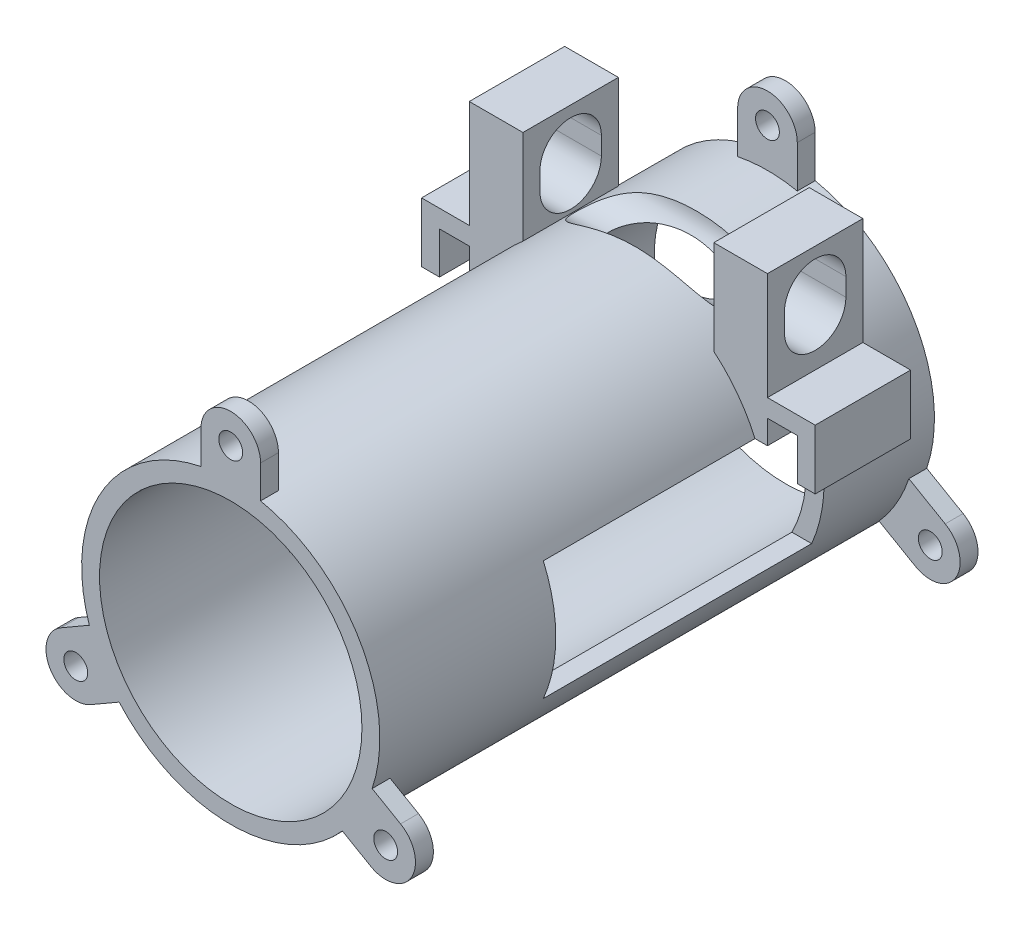
SolidWorks part; units mm, degrees
ref_plane "Front Plane" through (0, 0, 0) normal (0, 0, 1) x (1, 0, 0)
ref_plane "Top Plane" through (0, 0, 0) normal (0, 1, 0) x (1, 0, 0)
ref_plane "Right Plane" through (0, 0, 0) normal (1, 0, 0) x (0, 0, -1)
sketch "Sketch1" plane through (0, 0, 0) normal (0, 0, 1) x (1, 0, 0)
  circle A0 centre (0, 0) radius 22
  circle A1 centre (0, 0) radius 25
  dimension "D1" = 44
  dimension "D2" = 3
extrude "Boss-Extrude1" add sketch "Sketch1" along normal blind 40
ref_plane "Plane1" through (0, 0, 20) normal (0, 0, 1) x (1, 0, 0)
sketch "Sketch3" plane through (0, 0, 0) normal (1, 0, 0) x (0, 0, -1)
  line L0 (0, 25) -> (-40, 25) construction
  circle A0 centre (-20, 25) radius 5.15
  dimension "D1" = 10.3
extrude "Cut-Extrude1" cut sketch "Sketch3" against normal mid plane 50
sketch "Sketch4" plane through (0, 0, 20) normal (0, 0, 1) x (1, 0, 0)
  line L3 (0, 0) -> (50000, 0) construction
  line L4 (-19.776, 25) -> (49980.224, 25) construction
  line L5 (-16, 19.2094) -> (-16, 35)
  line L6 (-25, 0) -> (-25, 35)
  line L7 (-25, 35) -> (-16, 35)
  line L8 (0, 0) -> (0, 11.0861) construction
  arc A1 (-25, 0) -> (-16, 19.2094) centre (0, 0) cw
  circle A3 centre (0, 0) radius 25 construction
  point P14 (0, 0)
  point P15 (-25, -10.393)
  point P16 (0, 0)
  dimension "D1" = 9
  dimension "D2" = 35
extrude "Boss-Extrude2" add sketch "Sketch4" along normal mid plane 16
sketch "Sketch6" plane through (0, 0, 20) normal (0, 0, 1) x (1, 0, 0)
  line L0 (-25, 35) -> (-25, 0) construction
  line L1 (-25, 14) -> (-33, 14)
  line L2 (-25, 14) -> (-25, 17)
  line L3 (-25, 17) -> (-33, 17)
  line L4 (-33, 14) -> (-33, 17)
  line L5 (-25, 14) -> (-33, 17) construction
  line L6 (-25, 17) -> (-33, 14) construction
  line L7 (-33, 14) -> (-30, 14)
  line L8 (-33, 14) -> (-33, 7)
  line L9 (-33, 7) -> (-30, 7)
  line L10 (-30, 14) -> (-30, 7)
  line L11 (-33, 14) -> (-30, 7) construction
  line L12 (-33, 7) -> (-30, 14) construction
  point P4 (-29, 15.5)
  point P5 (-29, 10.725)
  point P6 (0, 0)
  point P13 (-31.5, 10.5)
  dimension "D1" = 8
  dimension "D2" = 3
  dimension "D3" = 7
  dimension "D4" = 3
  dimension "D5" = 7
sketch "Sketch5" plane through (-25, 0, 0) normal (-1, 0, 0) x (0, 0, 1)
  line L0 (20, -27.5) -> (20, 27.5) construction
  line L1 (20, 25) -> (20, 28) construction
  line L6 (14.85, 25) -> (14.85, 28)
  line L7 (25.15, 25) -> (25.15, 28)
  circle A0 centre (20, 25) radius 5.15 construction
  arc A1 (25.15, 25) -> (14.85, 25) centre (20, 25) ccw construction
  arc A2 (14.85, 25) -> (25.15, 25) centre (20, 25) ccw
  arc A3 (25.15, 28) -> (14.85, 28) centre (20, 28) ccw
  point P7 (20, 26.5)
  dimension "D1" = 3
extrude "Cut-Extrude3" cut sketch "Sketch5" against normal through all
extrude "Boss-Extrude3" add sketch "Sketch6" along normal mid plane 16 contours L10 L1 L8 L9 | L2 L1 L4 L3 region at (-31.5, 10.5, 20)
mirror "Mirror1" about plane through (0, 0, 0) normal (1, 0, 0) of "Cut-Extrude3", "Boss-Extrude3", "Boss-Extrude2"
sketch "Sketch7" plane through (0, 0, 40) normal (0, 0, 1) x (1, 0, 0)
  circle A0 centre (0, 0) radius 22
  circle A1 centre (0, 0) radius 25
extrude "Boss-Extrude4" add sketch "Sketch7" along normal blind 53
ref_plane "Plane2" through (-25, 0, 0) normal (-1, 0, 0) x (0, 0, 1)
sketch "Sketch8" plane through (-25, 0, 0) normal (-1, 0, 0) x (0, 0, 1)
  line L0 (20, -27.5) -> (20, 27.5) construction
  line L1 (18.5, 10) -> (63.5, 10)
  line L2 (18.5, 10) -> (18.5, -10)
  line L3 (18.5, -10) -> (63.5, -10)
  line L4 (63.5, 10) -> (63.5, -10)
  line L5 (18.5, 10) -> (63.5, -10) construction
  line L6 (18.5, -10) -> (63.5, 10) construction
  point P4 (41, 0)
  point P7 (0, 0)
  dimension "D1" = 21
  dimension "D2" = 45
  dimension "D3" = 20
extrude "Cut-Extrude4" cut sketch "Sketch8" against normal blind 50
sketch "Sketch9" plane through (0, 0, 0) normal (0, 0, -1) x (-1, 0, 0)
  line L0 (0, 0) -> (0, 31.533) construction
  line L1 (-5, 31.533) -> (-5, 24.4949)
  line L2 (5, 31.533) -> (5, 24.4949)
  circle A0 centre (0, 31.533) radius 2
  circle A1 centre (0, 31.533) radius 5
  circle A2 centre (0, 0) radius 25 construction
  arc A3 (-5, 24.4949) -> (5, 24.4949) centre (0, 0) cw
  circle A6 centre (0, 31.533) radius 2 construction
  point P13 (5, 24.4949)
  circle M3 centre (0, 0) radius 25
  dimension "D1" = 4
  dimension "D2" = 3
extrude "Boss-Extrude5" add sketch "Sketch9" against normal blind 3 contours A1 L1 M3 | A1 A3 A0 M3 | A1 L2 M3 region at (0, 26.4396, 0) region at (0, 36.3916, 0)
pattern_circular "CirPattern1" count 3 every 120 about axis through (0, 0, 0) along (0, 0, 1) of "Boss-Extrude5"
sketch "Sketch10" plane through (0, 0, 93) normal (0, 0, 1) x (1, 0, 0)
  line L0 (-5, 30) -> (-5, 24.4949)
  line L1 (5, 30) -> (5, 24.4949)
  line L2 (0, 0) -> (0, 30) construction
  circle A0 centre (0, 30) radius 2
  circle A1 centre (0, 30) radius 5
  arc A2 (-5, 24.4949) -> (5, 24.4949) centre (0, 0) cw
  circle A3 centre (0, 0) radius 25 construction
  circle M5 centre (0, 0) radius 25
  dimension "D2" = 4
  dimension "D3" = 30
  dimension "D1" = 3
extrude "Boss-Extrude6" add sketch "Sketch10" against normal blind 3 contours A1 A0 M5 | A1 L0 M5 | A1 L1 M5 region at (-3.8655, 25.9455, 93) region at (0, 34.8586, 93) region at (3.8655, 25.9455, 93)
pattern_circular "CirPattern2" count 3 every 120 about axis through (0, 0, 93) along (0, 0, 1) of "Boss-Extrude6"
